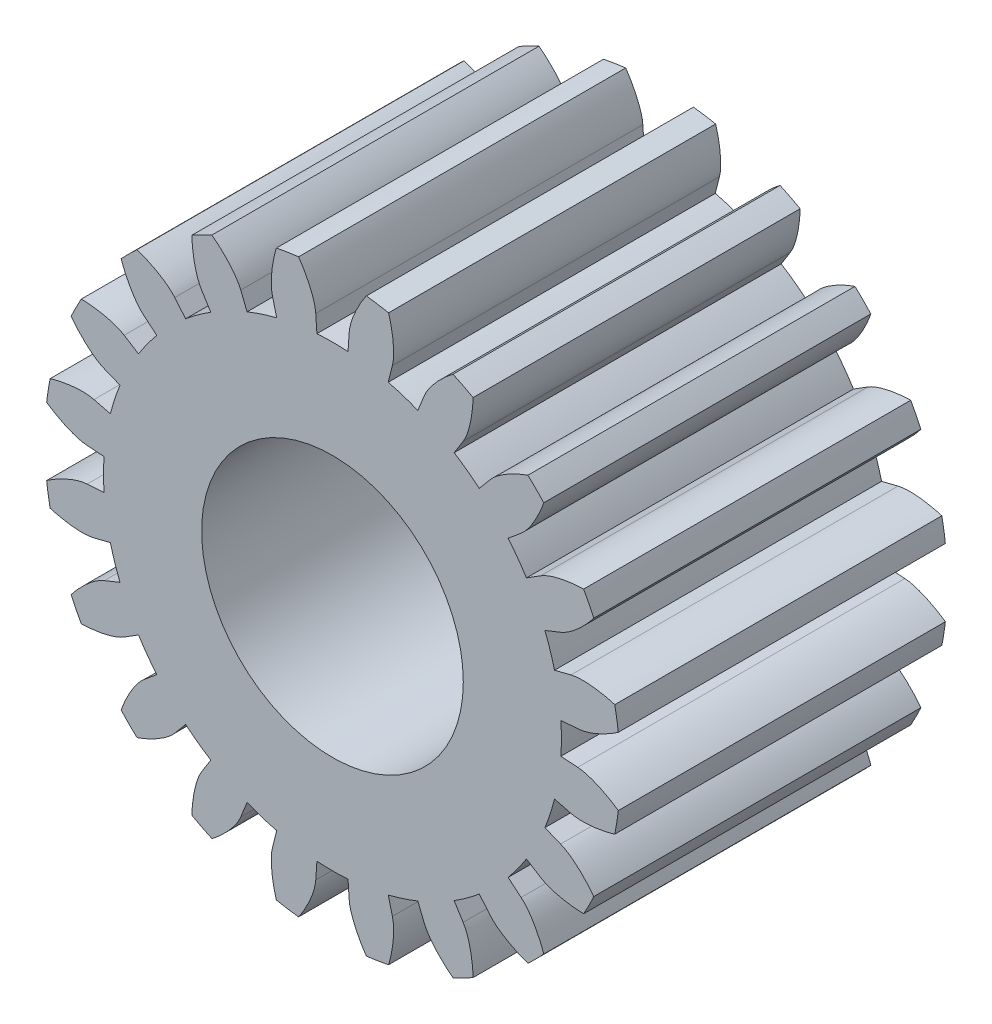
SolidWorks part; units mm, degrees
ref_plane "前视基准面" through (0, 0, 0) normal (0, 0, 1) x (1, 0, 0)
ref_plane "上视基准面" through (0, 0, 0) normal (0, 1, 0) x (1, 0, 0)
ref_plane "右视基准面" through (0, 0, 0) normal (1, 0, 0) x (0, 0, -1)
other "Configuration Table"
sketch "草图1" plane through (0, 0, 0) normal (0, 0, 1) x (1, 0, 0)
  line L0 (0, 0) -> (2, 0) construction
  line L1 (0, 0) -> (1.9938, 0.1569) construction
  line L2 (0, 0) -> (1.875, 0.1277)
  line L3 (1.9938, 0.1569) -> (1.9938, -0.1569) construction
  line L4 (0, 0) -> (1.875, -0.1277)
  circle A0 centre (0, 0) radius 2.2
  circle A1 centre (0, 0) radius 2 construction
  circle A2 centre (0, 0) radius 1.75
  circle A3 centre (0, 0) radius 1.8794 construction
  circle A4 centre (0, 0) radius 1
  spline S0 degree 4 poles (1.875, 0.1277) (1.8893, 0.1287) (1.929, 0.1344) (2.0025, 0.157) (2.1154, 0.2097) (2.2496, 0.2999) (2.4038, 0.439) (2.558, 0.6275) (2.6959, 0.8566) (2.809, 1.1216) (2.8885, 1.3983) (2.9362, 1.6822) (2.9548, 1.9837) (2.9388, 2.3574) (2.8628, 2.7975) (2.7005, 3.2908) (2.438, 3.8043) (2.1043, 4.2744) (1.7108, 4.6951) (1.2662, 5.062) (0.7817, 5.3723) (0.2626, 5.6242) (-0.2099, 5.7928) (-0.6312, 5.9005) (-0.9788, 5.9657) (-1.275, 6.0034) (-1.5146, 6.0246) (-1.7994, 6.0339) (-1.9848, 6.0333) (-2.2485, 6.0248) (-2.4456, 6.0069) (-2.6444, 5.9868) (-2.7432, 5.9706) (-2.8075, 5.9617) knots 0 0 0 0 0 0.005604 0.015718 0.02996 0.048734 0.068727 0.096889 0.125051 0.153212 0.181374 0.209535 0.237696 0.271429 0.327752 0.384075 0.440398 0.496721 0.553044 0.609367 0.66569 0.722013 0.778336 0.806497 0.834659 0.86282 0.890982 0.909091 0.931818 0.954545 0.977273 1 1 1 1 1 construction
  spline S1 degree 4 poles (1.875, 0.1277) (1.8893, 0.1287) (1.929, 0.1344) (2.0025, 0.157) (2.1154, 0.2097) (2.2496, 0.2999) (2.4038, 0.439) (2.558, 0.6275) (2.6959, 0.8566) (2.809, 1.1216) (2.8885, 1.3983) (2.9362, 1.6822) (2.9548, 1.9837) (2.9388, 2.3574) (2.8628, 2.7975) (2.7005, 3.2908) (2.438, 3.8043) (2.1043, 4.2744) (1.7108, 4.6951) (1.2662, 5.062) (0.7817, 5.3723) (0.2626, 5.6242) (-0.2099, 5.7928) (-0.6312, 5.9005) (-0.9788, 5.9657) (-1.275, 6.0034) (-1.5146, 6.0246) (-1.7328, 6.0317) (-1.8402, 6.033) (-1.8822, 6.033) knots 0 0 0 0 0 0.005604 0.015718 0.02996 0.048734 0.068727 0.096889 0.125051 0.153212 0.181374 0.209535 0.237696 0.271429 0.327752 0.384075 0.440398 0.496721 0.553044 0.609367 0.66569 0.722013 0.778336 0.806497 0.834659 0.86282 0.890982 0.909091 0.909091 0.909091 0.909091 0.909091
  spline S2 degree 4 poles (1.875, -0.1277) (1.8893, -0.1287) (1.929, -0.1344) (2.0025, -0.157) (2.1154, -0.2097) (2.2496, -0.2999) (2.4038, -0.439) (2.558, -0.6275) (2.6959, -0.8566) (2.809, -1.1216) (2.8885, -1.3983) (2.9362, -1.6822) (2.9548, -1.9837) (2.9388, -2.3574) (2.8628, -2.7975) (2.7005, -3.2908) (2.438, -3.8043) (2.1043, -4.2744) (1.7108, -4.6951) (1.2662, -5.062) (0.7817, -5.3723) (0.2626, -5.6242) (-0.2099, -5.7928) (-0.6312, -5.9005) (-0.9788, -5.9657) (-1.275, -6.0034) (-1.5146, -6.0246) (-1.7994, -6.0339) (-1.9848, -6.0333) (-2.2485, -6.0248) (-2.4456, -6.0069) (-2.6444, -5.9868) (-2.7432, -5.9706) (-2.8075, -5.9617) knots 0 0 0 0 0 0.005604 0.015718 0.02996 0.048734 0.068727 0.096889 0.125051 0.153212 0.181374 0.209535 0.237696 0.271429 0.327752 0.384075 0.440398 0.496721 0.553044 0.609367 0.66569 0.722013 0.778336 0.806497 0.834659 0.86282 0.890982 0.909091 0.931818 0.954545 0.977273 1 1 1 1 1 construction
  spline S3 degree 4 poles (1.875, -0.1277) (1.8893, -0.1287) (1.929, -0.1344) (2.0025, -0.157) (2.1154, -0.2097) (2.2496, -0.2999) (2.4038, -0.439) (2.558, -0.6275) (2.6959, -0.8566) (2.809, -1.1216) (2.8885, -1.3983) (2.9362, -1.6822) (2.9548, -1.9837) (2.9388, -2.3574) (2.8628, -2.7975) (2.7005, -3.2908) (2.438, -3.8043) (2.1043, -4.2744) (1.7108, -4.6951) (1.2662, -5.062) (0.7817, -5.3723) (0.2626, -5.6242) (-0.2099, -5.7928) (-0.6312, -5.9005) (-0.9788, -5.9657) (-1.275, -6.0034) (-1.5146, -6.0246) (-1.7328, -6.0317) (-1.8402, -6.033) (-1.8822, -6.033) knots 0 0 0 0 0 0.005604 0.015718 0.02996 0.048734 0.068727 0.096889 0.125051 0.153212 0.181374 0.209535 0.237696 0.271429 0.327752 0.384075 0.440398 0.496721 0.553044 0.609367 0.66569 0.722013 0.778336 0.806497 0.834659 0.86282 0.890982 0.909091 0.909091 0.909091 0.909091 0.909091
  point P15 (1.9938, 0)
  dimension "齿顶圆直径" = 4.4
  dimension "分度圆直径" = 4
  dimension "齿根圆直径" = 3.5
  dimension "基圆直径" = 3.7588
  dimension "内孔直径" = 2
  dimension "渐近线镜像线夹角" = 4.5
extrude "凸台-拉伸1" add sketch "草图1" along normal blind 2.5 contours A0 | A4
extrude "切除-拉伸1" cut sketch "草图1<3>" along normal through all contours A2 S3 A0 S1 region at (2.0041, 0, 0)
sketch "草图1<3>" plane through (0, 0, 0) normal (0, 0, 1) x (1, 0, 0) same geometry as "草图1"
pattern_circular "阵列(圆周)1" count 20 every 18 about axis through (0, 0, 2.5) along (0, 0, 1) of "切除-拉伸1"
equation "\"m\" = 0.2'模数"
equation "\"z\" = 20'齿数"
equation "\"a\"= 20度'压力角"
equation "\"d\"= \"m\" * \"z\"'分度圆直径"
equation "\"da\"= ( \"z\" + 2 ) * \"m\"'齿顶圆直径"
equation "\"df\"= ( \"z\" - 2.5 ) * \"m\"'齿根圆直径"
equation "\"s\"= 0.5 * PI * \"m\"'分度圆齿厚"
equation "\"r\"= 0.38 * \"m\"'齿根圆角"
equation "\"B\"= 0.3 * \"d\"'齿厚"
equation "\"db\"= \"m\" * \"z\" * cos ( \"a\" )'基圆直径"
equation "\"rb\"= \"db\" / 2'基圆半径"
equation "\"齿顶圆直径@草图1\"= \"da\""
equation "\"分度圆直径@草图1\"= \"d\""
equation "\"齿根圆直径@草图1\"= \"df\""
equation "\"基圆直径@草图1\"= \"db\""
equation "\"渐近线镜像线夹角@草图1\"= 360 / 4 / \"z\""
equation "\"h\"= 2.5'齿轮厚度"
equation "\"ir\"= 2'内孔直径"
equation "\"内孔直径@草图1\"= \"ir\""
equation "\"齿轮厚@凸台-拉伸1\"= \"h\""
equation "\"齿轮夹角@阵列(圆周)1\"= 360 / \"z\""
equation "\"齿数@阵列(圆周)1\"= \"z\""
